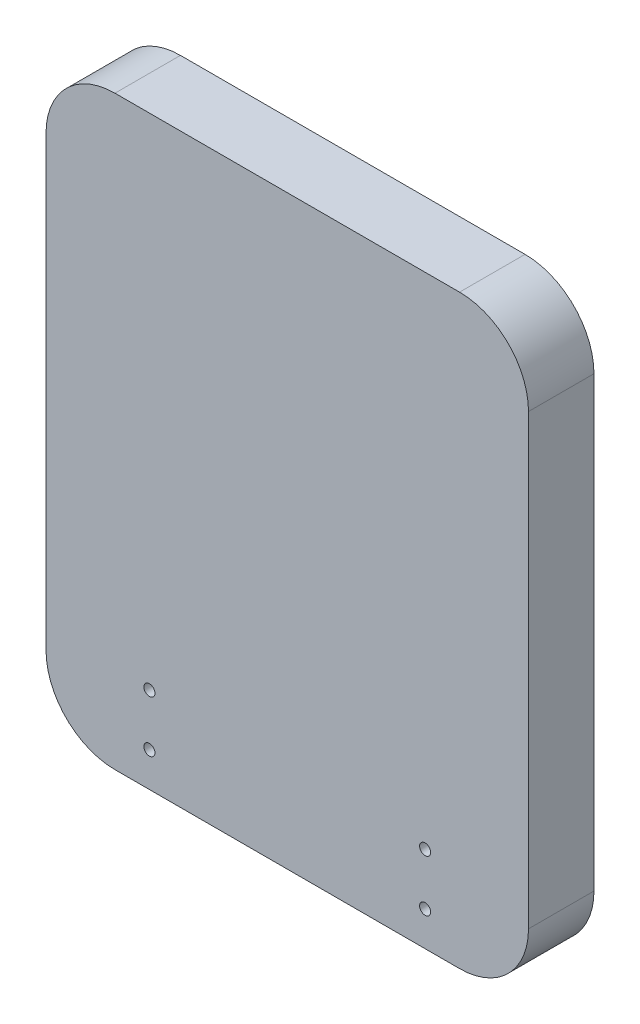
SolidWorks part; units mm, degrees
note: The reader was unsure of these and kept them because the rebuilt part matched: shared geometry of "Sketch6<3>", "Sketch7<3>".
ref_plane "Front Plane" through (0, 0, 0) normal (0, 0, 1) x (1, 0, 0)
ref_plane "Top Plane" through (0, 0, 0) normal (0, 1, 0) x (1, 0, 0)
ref_plane "Right Plane" through (0, 0, 0) normal (1, 0, 0) x (0, 0, -1)
sketch "Sketch1" plane through (0, 0, 0) normal (0, 0, 1) x (1, 0, 0)
  line L1 (-72.8773, 101.0393) -> (67.1227, 101.0393)
  line L2 (-72.8773, 101.0393) -> (-72.8773, -68.9607)
  line L3 (-72.8773, -68.9607) -> (67.1227, -68.9607)
  line L4 (67.1227, 101.0393) -> (67.1227, -68.9607)
  line L5 (-72.8773, 101.0393) -> (67.1227, -68.9607) construction
  line L6 (-72.8773, -68.9607) -> (67.1227, 101.0393) construction
  line L7 (-2.8473, -44.4787) -> (-2.9073, -44.4787) construction
  line L8 (-2.9073, -44.3515) -> (-2.9073, -44.6058) construction
  line L9 (-2.8473, -44.6058) -> (-2.8473, -44.3515) construction
  line L10 (-2.8773, -44.4787) -> (-2.8773, 16.0393) construction
  line L12 (48.1227, -44.4607) -> (-10.8773, -44.4607) construction
  line L16 (-2.9073, -44.3515) -> (-2.9073, -44.6058) construction
  line L17 (-2.8473, -44.6058) -> (-2.8473, -44.3515) construction
  point P0 (-2.8773, 16.0393)
  dimension "D1" = 170
  dimension "D2" = 140
  dimension "D3" = 24.5
extrude "Boss-Extrude1" add sketch "Sketch1" along normal blind 5 and the other way blind 14
fillet "Fillet1" radius 20 4 edges at (-72.8773, 101.0393, -4.5) (67.1227, 101.0393, -4.5) (67.1227, -68.9607, -4.5) (-72.8773, -68.9607, -4.5)
shell "Shell2" thickness 4
ref_plane "Plane1" through (-2.8773, 0, 0) normal (1, 0, 0) x (0, 0, -1)
ref_plane "Plane2" through (0, 16.0393, 0) normal (0, -1, 0) x (-1, 0, 0)
sketch "Sketch2" plane through (0, 0, 0) normal (0, 0, -1) x (-1, 0, 0)
  arc A0 (10.3773, -16.6107) -> (10.3773, -19.3107) centre (10.3773, -17.9607) ccw construction
  arc A1 (10.3773, -16.6107) -> (10.3773, -19.3107) centre (10.3773, -17.9607) ccw construction
  arc A2 (10.3773, -39.6107) -> (10.3773, -42.3107) centre (10.3773, -40.9607) ccw construction
  arc A3 (10.3773, -39.6107) -> (10.3773, -42.3107) centre (10.3773, -40.9607) ccw construction
  arc A4 (-47.6227, -39.6107) -> (-47.6227, -42.3107) centre (-47.6227, -40.9607) ccw construction
  arc A5 (-47.6227, -39.6107) -> (-47.6227, -42.3107) centre (-47.6227, -40.9607) ccw construction
  arc A6 (-47.6227, -16.6107) -> (-47.6227, -19.3107) centre (-47.6227, -17.9607) ccw construction
  arc A7 (-47.6227, -16.6107) -> (-47.6227, -19.3107) centre (-47.6227, -17.9607) ccw construction
  circle A8 centre (10.3773, -40.9607) radius 1.8
  circle A9 centre (10.3773, -17.9607) radius 1.8
  circle A10 centre (-47.6227, -17.9607) radius 1.8
  circle A11 centre (-47.6227, -40.9607) radius 1.8
  dimension "D1" = 3.6
extrude "Cut-Extrude1" cut sketch "Sketch2" against normal blind 4.5
sketch "Sketch3" plane through (0, 0, 0) normal (0, 0, -1) x (-1, 0, 0)
  circle A0 centre (21.3773, -5.5607) radius 1.4 construction
  circle A1 centre (21.3773, -5.5607) radius 1.4 construction
  circle A2 centre (-58.6227, -5.5607) radius 1.4 construction
  circle A3 centre (-58.6227, -5.5607) radius 1.4 construction
  circle A4 centre (-58.6227, -5.5607) radius 1.8
  circle A5 centre (21.3773, -5.5607) radius 1.8
  dimension "D1" = 3.6
extrude "Cut-Extrude3" cut sketch "Sketch3" against normal blind 4.5
sketch "Sketch4" plane through (0, -68.9607, 0) normal (0, -1, 0) x (1, 0, 0)
  line L0 (-2.8773, -14) -> (-2.8773, 5) construction
  line L1 (-52.8773, -14) -> (47.1227, -14) construction
  line L2 (-52.8773, 5) -> (47.1227, 5) construction
  line L3 (48.1227, -3.78) -> (-10.8773, -3.78) construction
  line L4 (0.3727, -5.08) -> (-6.1273, -5.08)
  line L5 (0.3727, -5.08) -> (0.3727, -14)
  line L6 (0.3727, -14) -> (-6.1273, -14)
  line L7 (-6.1273, -5.08) -> (-6.1273, -14)
  line L8 (0.3727, -5.08) -> (-6.1273, -14) construction
  line L9 (0.3727, -14) -> (-6.1273, -5.08) construction
  line L10 (48.1227, -3.78) -> (-10.8773, -3.78) construction
  circle A0 centre (-2.8773, -5.08) radius 3.25
  point P6 (-2.8773, -9.54)
  line M6 (-52.8773, -14) -> (47.1227, -14)
  dimension "D1" = 1.3
  dimension "D2" = 6.5
extrude "Cut-Extrude4" cut sketch "Sketch4" against normal up to surface (4 mm away) contours L4 A0 | L4 A0 | A0 L7 L5 M6 up to face at (-2.8773, -64.9607, -7)
sketch "Sketch6" plane through (0, 0, -14) normal (0, 0, -1) x (-1, 0, 0)
  line L0 (-58.4364, 92.3531) -> (-47.1227, 81.0393) construction
  line L1 (-63.1227, 81.0393) -> (-53.5317, 85.0139)
  line L2 (-47.1227, 97.0393) -> (-51.0972, 87.4483)
  arc A0 (-47.1227, 97.0393) -> (-63.1227, 81.0393) centre (-47.1227, 81.0393) ccw construction
  circle A1 centre (-55.2544, 89.1711) radius 4.5
  circle A2 centre (-55.2544, 89.1711) radius 2.2
  arc M7 (-63.1227, 81.0393) -> (-47.1227, 97.0393) centre (-47.1227, 81.0393) cw
  dimension "D1" = 4.4
  dimension "D2" = 9
extrude "Boss-Extrude2" add sketch "Sketch6" against normal up to surface (14 mm away) contours A1 L1 M7 | L0 A1 A2 | A1 L0 A2 | A1 L2 M7 | L0 A2 | A2 L0 up to face at (56.8227, -5.5607, 0)
extrude "Cut-Extrude5" cut sketch "Sketch6<3>" against normal blind 4.5 contours A2 L0 | L0 A2
sketch "Sketch6<3>" plane through (0, 0, -14) normal (0, 0, -1) x (-1, 0, 0) same geometry as "Sketch6"
mirror "Mirror1" about plane through (0, 16.0393, 0) normal (0, -1, 0) of "Cut-Extrude5", "Boss-Extrude2" second plane through (-2.8773, 0, 0) second plane normal (1, 0, 0)
fillet "Fillet2" radius 3 6 edges at (63.1227, 81.0393, -7) (63.1227, -48.9607, -7) (-68.8773, 81.0393, -7) (-68.8773, -48.9607, -7) (-52.8773, 97.0393, -7) (47.1227, 97.0393, -7)
chamfer "Chamfer1" distance 0.5 angle 45 10 edges at (53.0544, 89.1711, -14) (-58.809, 89.1711, -14) (53.0544, -57.0924, -14) (-58.809, -57.0924, -14) (45.8227, -40.9607, 0) (45.8227, -17.9607, 0) (-12.1773, -17.9607, 0) (-12.1773, -40.9607, 0) (56.8227, -5.5607, 0) (-23.1773, -5.5607, 0)
sketch "Sketch7" plane through (0, 0, 0) normal (0, 0, -1) x (-1, 0, 0)
  line L0 (-37.1227, -58.9607) -> (-37.1227, -43.9607) construction
  line L1 (52.8773, -68.9607) -> (-47.1227, -68.9607) construction
  line L2 (-67.1227, -48.9607) -> (-67.1227, 81.0393) construction
  line L4 (-37.1227, -47.4248) -> (-34.1227, -45.6927)
  line L5 (-34.1227, -45.6927) -> (-34.1227, -42.2286)
  line L6 (-34.1227, -42.2286) -> (-37.1227, -40.4966)
  line L7 (-37.1227, -40.4966) -> (-40.1227, -42.2286)
  line L8 (-40.1227, -42.2286) -> (-40.1227, -45.6927)
  line L9 (-40.1227, -45.6927) -> (-37.1227, -47.4248)
  line L10 (-37.1172, -55.4966) -> (-40.1199, -57.2239)
  line L11 (-40.1199, -57.2239) -> (-40.1254, -60.688)
  line L12 (-40.1254, -60.688) -> (-37.1282, -62.4247)
  line L13 (-37.1282, -62.4247) -> (-34.1254, -60.6974)
  line L14 (-34.1254, -60.6974) -> (-34.12, -57.2334)
  line L15 (-34.12, -57.2334) -> (-37.1172, -55.4966)
  circle A0 centre (-37.1227, -58.9607) radius 1.6
  circle A1 centre (-37.1227, -43.9607) radius 1.6
  circle A2 centre (-37.1227, -43.9607) radius 3 construction
  circle A3 centre (-37.1227, -58.9607) radius 3 construction
  dimension "D1" = 3.2
  dimension "D2" = 15
  dimension "D3" = 10
  dimension "D4" = 30
  dimension "D5" = 6
extrude "Cut-Extrude6" cut sketch "Sketch7" against normal through all contours A0 | A1
extrude "Cut-Extrude7" cut sketch "Sketch7<3>" against normal blind 2.5
sketch "Sketch7<3>" plane through (0, 0, 0) normal (0, 0, -1) x (-1, 0, 0) same geometry as "Sketch7"
mirror "Mirror2" about plane through (-2.8773, 0, 0) normal (1, 0, 0) of "Cut-Extrude6", "Cut-Extrude7"
